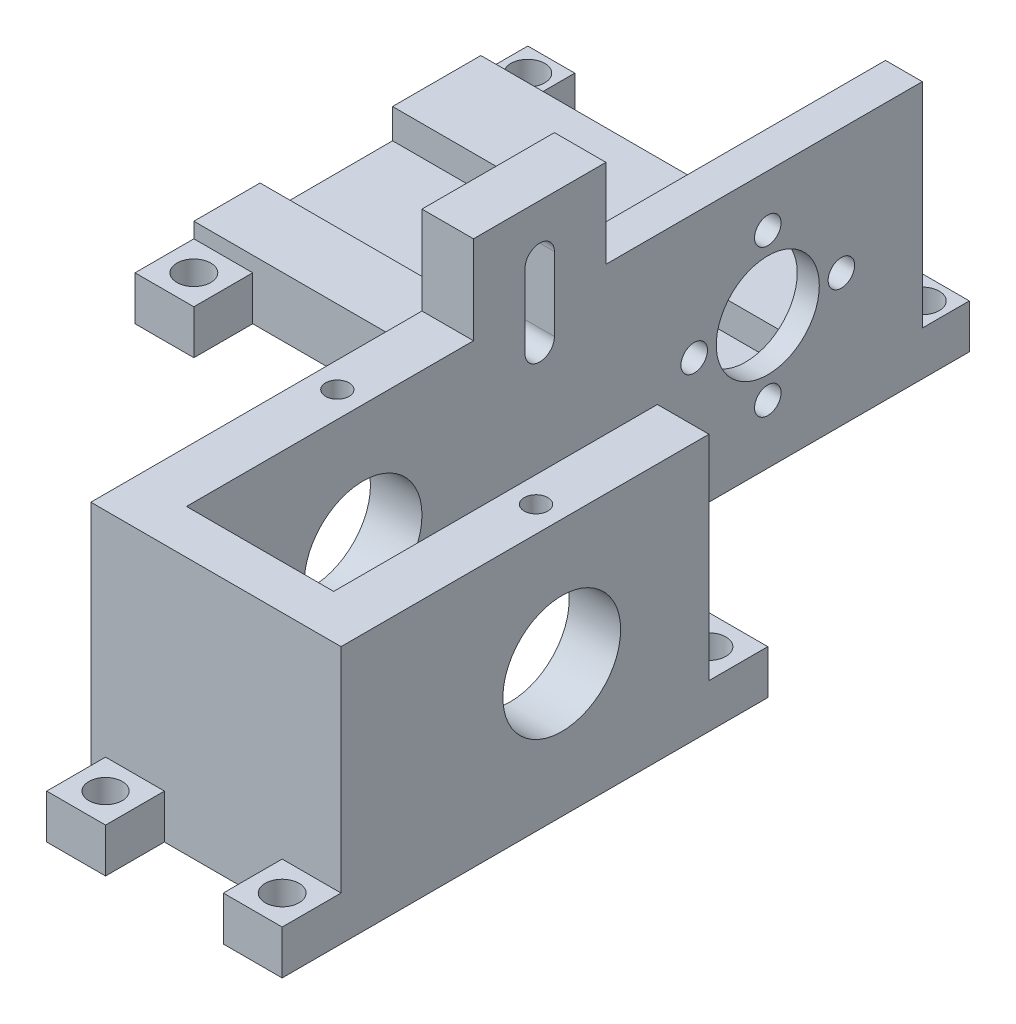
SolidWorks part; units mm, degrees
note: The reader was unsure of these and kept them because the rebuilt part matched: shared geometry of "Esquisse4<4>".
ref_plane "Plan de face" through (0, 0, 0) normal (0, 0, 1) x (1, 0, 0)
ref_plane "Plan de dessus" through (0, 0, 0) normal (0, 1, 0) x (1, 0, 0)
ref_plane "Plan de droite" through (0, 0, 0) normal (1, 0, 0) x (0, 0, -1)
sketch "Esquisse1" plane through (0, 0, 0) normal (0, 1, 0) x (1, 0, 0)
  line L0 (0, 0) -> (17, 0)
  line L1 (0, 0) -> (-15, 0)
  line L2 (-15, 0) -> (-15, 50)
  line L3 (-15, 50) -> (-10, 50)
  line L4 (-10, 50) -> (-10, 6)
  line L5 (17, 0) -> (17, 50)
  line L6 (17, 50) -> (10, 50)
  line L9 (-15, 0) -> (-15, 106)
  line L10 (-10, 76) -> (-70, 76)
  line L11 (-70, 76) -> (-70, 106)
  line L12 (-70, 106) -> (-10, 106)
  line L17 (-10, 50) -> (-10, 106) construction
  line L18 (-10, 106) -> (-15, 106)
  line L19 (-10, 106) -> (-10, 76)
  line L20 (-10, 76) -> (-10, 50)
  line L21 (10, 50) -> (10, 6)
  line L22 (-17, 0) -> (-17, 76)
  line L24 (-17, 0) -> (-15, 0)
  line L25 (-10, 6) -> (10, 6)
extrude "Boss.-Extru.1" add sketch "Esquisse1" along normal blind 47
sketch "Esquisse2" plane through (17, 0, 0) normal (1, 0, 0) x (0, 0, -1)
  line L0 (0, 0) -> (30, 0) construction
  line L2 (0, 0) -> (106, 0) construction
  line L3 (30, 0) -> (30, 18) construction
  circle A0 centre (30, 18) radius 8
sketch "Esquisse3" plane through (-15, 0, 0) normal (-1, 0, 0) x (0, 0, 1)
  line L0 (0, 0) -> (-54, 0) construction
  line L1 (0, 0) -> (-106, 0) construction
  line L3 (0, 47) -> (-106, 47) construction
  line L4 (-54, 47) -> (-54, 40) construction
  line L5 (-52, 40) -> (-52, 30)
  line L6 (-52, 30) -> (-56, 30) construction
  line L7 (-56, 30) -> (-56, 40)
  circle A0 centre (-54, 40) radius 2
  circle A1 centre (-54, 30) radius 2
extrude "Enlèv. mat.-Extru.2" cut sketch "Esquisse3" against normal blind 50 contours A1 L5 A0 L7 | A0 | A1
sketch "Esquisse4" plane through (-10, 0, 0) normal (1, 0, 0) x (0, 0, -1)
  line L0 (106, 0) -> (67, 0)
  line L1 (106, 0) -> (6, 0) construction
  line L2 (85, 18) -> (85, 8) construction
  line L3 (85, 18) -> (85, 28) construction
  line L4 (85, 28) -> (85, 18) construction
  line L5 (85, 18) -> (75, 18) construction
  line L6 (67, 0) -> (76, 0) construction
  line L7 (85, 18) -> (95, 18) construction
  line L8 (106, 0) -> (94, 0) construction
  line L9 (94, 0) -> (94, 8.0723)
  line L10 (94, 8.0723) -> (106, 8.0723)
  line L11 (106, 47) -> (106, 0) construction
  line L12 (94, 0) -> (85, 0) construction
  line L13 (76, 8.0723) -> (76, 0)
  line L14 (76, 8.0723) -> (67, 8.0723)
  line L15 (67, 8.0723) -> (67, 0)
  line L16 (106, 8.0723) -> (106, 0)
  line L17 (106, 8.0723) -> (106, 0)
  line L18 (94, 0) -> (106, 0)
  line L19 (76, 0) -> (76, 4)
  line L20 (76, 4) -> (94, 4.0361)
  line L21 (94, 4.0361) -> (94, 0)
  circle A0 centre (85, 18) radius 13.4
  circle A1 centre (75, 18) radius 1.8
  circle A2 centre (85, 8) radius 1.8
  circle A3 centre (95, 18) radius 1.8
  circle A4 centre (85, 28) radius 1.8
  circle A5 centre (85, 18) radius 7
  line M8 (6, 0) -> (106, 0)
  line M9 (106, 0) -> (106, 47)
extrude "Enlèv. mat.-Extru.3" cut sketch "Esquisse4" against normal blind 5 contours A2 | A3 | A1 | A4 | A5
extrude "Boss.-Extru.2" add sketch "Esquisse4<4>" against normal blind 60 contours L10 L9 L0 M9 | L14 L15 L13 M8 | L20 L13 L0 L9
sketch "Esquisse4<4>" plane through (-10, 0, 0) normal (1, 0, 0) x (0, 0, -1) same geometry as "Esquisse4"
sketch "Esquisse11" plane through (0, 0, 0) normal (0, -1, 0) x (1, 0, 0)
  line L0 (17, 0) -> (17, 8)
  line L1 (17, 8) -> (9, 8)
  line L2 (9, 8) -> (9, 0)
  line L3 (17, 0) -> (-15, 0) construction
  line L4 (9, 0) -> (17, 0)
  line L5 (-15, 0) -> (-15, 8)
  line L6 (-15, 8) -> (-7, 8)
  line L7 (-7, 8) -> (-7, 0)
  line L8 (-7, 0) -> (-15, 0)
  line L9 (-70, -67) -> (-70, -59)
  line L10 (-70, -59) -> (-62, -59)
  line L11 (-62, -59) -> (-62, -67)
  line L12 (-70, -67) -> (-15, -67) construction
  line L13 (-10, -106) -> (-10, -112.3846)
  line L14 (-10, -112.3846) -> (-16.3846, -112.3846)
  line L15 (-16.3846, -112.3846) -> (-16.3846, -106)
  line L16 (-70, -106) -> (-10, -106) construction
  line L17 (-70, -106) -> (-70, -112.3846)
  line L18 (-70, -112.3846) -> (-63.6154, -112.3846)
  line L19 (-63.6154, -112.3846) -> (-63.6154, -106)
  line L20 (-63.6154, -106) -> (-70, -106)
  line L21 (-16.3846, -106) -> (-10, -106)
  line L22 (-62, -67) -> (-70, -67)
  line L23 (-70, -59) -> (-62, -67) construction
  line L24 (-62, -59) -> (-70, -67) construction
  line L25 (-70, -106) -> (-63.6154, -112.3846) construction
  line L26 (-63.6154, -106) -> (-70, -112.3846) construction
  line L27 (-16.3846, -112.3846) -> (-10, -106) construction
  line L28 (-16.3846, -106) -> (-10, -112.3846) construction
  line L29 (-15, 8) -> (-7, 0) construction
  line L30 (-15, 0) -> (-7, 8) construction
  line L31 (9, 8) -> (17, 0) construction
  line L32 (17, 8) -> (9, 0) construction
  line L47 (17, -50) -> (17, -58)
  line L48 (17, -58) -> (9, -58)
  line L49 (9, -58) -> (9, -46)
  line L50 (9, -46) -> (10, -46)
  line L52 (10, -50) -> (10, -6) construction
  line L55 (17, -58) -> (9, -50) construction
  line L56 (9, -50) -> (9, -58) construction
  line L57 (17, -50) -> (9, -58) construction
  line L58 (-15, -67) -> (-15, -106) construction
  line L59 (-15, -106) -> (-23, -106)
  circle A2 centre (-11, 4) radius 2.268
  circle A3 centre (13, 4) radius 2.3
  circle A4 centre (-66, -63) radius 2.3
  circle A5 centre (-66.8077, -109.1923) radius 2.3
  circle A6 centre (-13.1923, -109.1923) radius 2.3
  circle A8 centre (13, -54) radius 2.3
  point P33 (0, 0)
extrude "Boss.-Extru.6" add sketch "Esquisse11" against normal blind 6
sketch "Esquisse12" plane through (-15, 0, 0) normal (-1, 0, 0) x (0, 0, 1)
  line L0 (0, 47) -> (0, 35)
  line L1 (0, 47) -> (0, 6) construction
  line L2 (0, 35) -> (-45, 35)
  line L3 (-45, 35) -> (-45, 47)
  line L4 (0, 47) -> (-106, 47) construction
  line L8 (-106, 47) -> (-106, 8.0723) construction
  line L9 (-106, 35) -> (-106, 47)
  line L10 (-106, 47) -> (0, 47)
  line L11 (-45, 47) -> (-63, 47)
  line L12 (-63, 47) -> (-63, 35)
  line L13 (-106, 35) -> (-63, 35)
  line M9 (0, 6) -> (0, 47)
  line M10 (0, 47) -> (-106, 47)
  line M11 (-106, 47) -> (-106, 8.0723)
extrude "Enlèv. mat.-Extru.5" cut sketch "Esquisse12" against normal blind 50 contours L13 L12 L10 M11 | L3 L2 M9 M10
sketch "Esquisse13" plane through (17, 0, 0) normal (1, 0, 0) x (0, 0, -1)
  line L0 (45, 35) -> (50, 35)
  line L1 (50, 47) -> (50, 6) construction
  line L2 (50, 35) -> (50, 47)
  line L3 (50, 47) -> (45, 47)
  line L4 (45, 47) -> (45, 35)
extrude "Enlèv. mat.-Extru.6" cut sketch "Esquisse13" against normal blind 20
sketch "Esquisse24" plane through (-10, 0, 0) normal (1, 0, 0) x (0, 0, -1)
  circle A0 centre (85, 18) radius 13.4
sketch "Esquisse25" plane through (-15, 0, 0) normal (-1, 0, 0) x (0, 0, 1)
  circle A0 centre (-85, 18) radius 13.4
extrude "Enlèv. mat.-Extru.8" cut sketch "Esquisse25" against normal blind 2
sketch "Esquisse26" plane through (0, 35, 0) normal (0, 1, 0) x (1, 0, 0)
  line L0 (17, 0) -> (17, 30) construction
  line L1 (17, 0) -> (17, 50) construction
  line L2 (17, 30) -> (10, 30) construction
  line L4 (-15, 0) -> (-15, 30) construction
  line L5 (-15, 0) -> (-15, 45) construction
  line L9 (10, 50) -> (10, 6) construction
  circle A2 centre (13.5, 30) radius 1.6
extrude "Enlèv. mat.-Extru.9" cut sketch "Esquisse26" against normal blind 10
sketch "Esquisse27" plane through (-15, 0, 0) normal (-1, 0, 0) x (0, 0, 1)
  line L0 (0, 35) -> (0, 0)
  line L1 (-63, 0) -> (0, 0)
  line L2 (8, 0) -> (-67, 0) construction
  line L3 (0, 35) -> (-45, 35)
  line L4 (-45, 35) -> (-45, 47)
  line L5 (-45, 47) -> (-63, 47)
  line L6 (-63, 47) -> (-63, 0)
extrude "Boss.-Extru.7" add sketch "Esquisse27" along normal blind 2
extrude "Enlèv. mat.-Extru.10" cut sketch "Esquisse2" against normal blind 60
sketch "Esquisse28" plane through (-10, 0, 0) normal (1, 0, 0) x (0, 0, -1)
  circle A0 centre (85, 28) radius 3
  circle A1 centre (75, 18) radius 3
  circle A2 centre (95, 18) radius 3
  circle A3 centre (85, 8) radius 3
sketch "Esquisse30" plane through (0, 35, 0) normal (0, 1, 0) x (1, 0, 0)
  line L1 (-17, 0) -> (-17, 45) construction
  line L2 (-17, 30) -> (-10, 30) construction
  line L3 (-10, 45) -> (-10, 6) construction
  circle A0 centre (-13.5, 30) radius 1.6
extrude "Enlèv. mat.-Extru.18" cut sketch "Esquisse30" against normal blind 10
